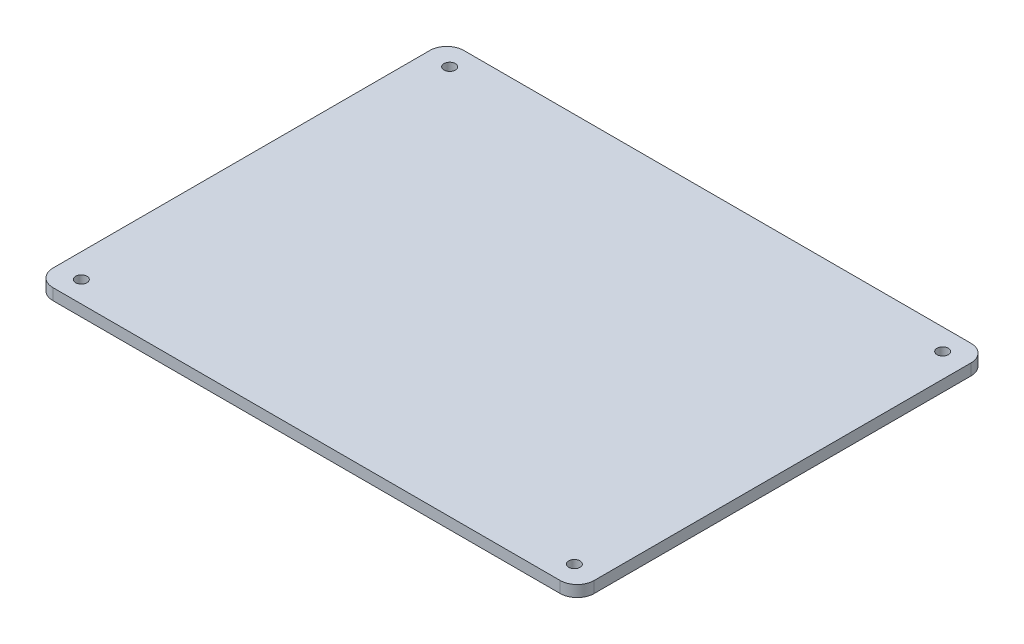
SolidWorks part; units mm, degrees
ref_plane "Спереди" through (0, 0, 0) normal (0, 0, 1) x (1, 0, 0)
ref_plane "Сверху" through (0, 0, 0) normal (0, 1, 0) x (1, 0, 0)
ref_plane "Справа" through (0, 0, 0) normal (1, 0, 0) x (0, 0, -1)
sketch "Эскиз1" plane through (0, 0, 0) normal (0, 1, 0) x (1, 0, 0)
  line L0 (-1000, 0) -> (49000, 0) construction
  line L1 (0, -1000) -> (0, 49000) construction
  line L2 (-1000, -35) -> (49000, -35) construction
  line L3 (-1000, 35) -> (49000, 35) construction
  line L4 (46.5, -1000) -> (46.5, 49000) construction
  line L5 (-46.5, -1000) -> (-46.5, 49000) construction
  line L10 (-47.75, -33.25) -> (-47.75, 33.25)
  line L11 (-44.75, -36.25) -> (44.75, -36.25)
  line L12 (47.75, -33.25) -> (47.75, 33.25)
  line L13 (-44.75, 36.25) -> (44.75, 36.25)
  line L15 (-47.75, -1000) -> (-47.75, 49000) construction
  line L16 (-1000, -36.25) -> (49000, -36.25) construction
  line L17 (-1000, 36.25) -> (49000, 36.25) construction
  line L18 (47.75, -1000) -> (47.75, 49000) construction
  arc A0 (-44.75, 36.25) -> (-47.75, 33.25) centre (-44.75, 33.25) ccw
  arc A1 (47.75, 33.25) -> (44.75, 36.25) centre (44.75, 33.25) ccw
  arc A2 (44.75, -36.25) -> (47.75, -33.25) centre (44.75, -33.25) ccw
  arc A3 (-44.75, -36.25) -> (-47.75, -33.25) centre (-44.75, -33.25) cw
  dimension "D5" = 3
  dimension "D1" = 1.25
  dimension "D2" = 1.25
  dimension "D3" = 1.25
  dimension "D4" = 1.25
extrude "Бобышка-Вытянуть1" add sketch "Эскиз1" along normal blind 2
sketch "Эскиз2" plane through (0, 2, 0) normal (0, 1, 0) x (1, 0, 0)
  line L0 (0, -1000) -> (0, 49000) construction
  line L1 (-1000, 0) -> (49000, 0) construction
  line L2 (43.5, -1000) -> (43.5, 49000) construction
  line L3 (-43.5, -1000) -> (-43.5, 49000) construction
  line L4 (-1000, -32.5) -> (49000, -32.5) construction
  line L5 (-1000, 32.5) -> (49000, 32.5) construction
  circle A0 centre (-43.5, 32.5) radius 2.5
  circle A1 centre (43.5, 32.5) radius 2.5
  circle A2 centre (43.5, -32.5) radius 2.5
  circle A3 centre (-43.5, -32.5) radius 2.5
sketch "Эскиз3" plane through (0, 5, 0) normal (0, 1, 0) x (1, 0, 0)
  circle A0 centre (-43.5, 32.5) radius 1
  circle A1 centre (-43.5, -32.5) radius 1
  circle A2 centre (43.5, -32.5) radius 1
  circle A3 centre (43.5, 32.5) radius 1
extrude "Вырез-Вытянуть1" cut sketch "Эскиз3" against normal blind 13 and the other way blind 3
sketch "Эскиз4" plane through (0, 0, 0) normal (0, -1, 0) x (1, 0, 0)
  line L0 (-1000, 0) -> (49000, 0) construction
  line L1 (0, -1000) -> (0, 49000) construction
  line L2 (19, -1000) -> (19, 49000) construction
  line L3 (-19, -1000) -> (-19, 49000) construction
  line L4 (-1000, -7) -> (49000, -7) construction
  line L5 (-1000, 7) -> (49000, 7) construction
  line L6 (-19, 7) -> (19, 7)
  line L7 (19, 7) -> (19, -7)
  line L8 (19, -7) -> (-19, -7)
  line L9 (-19, -7) -> (-19, 7)
extrude "Бобышка-Вытянуть3" add sketch "Эскиз4" along normal blind 3
sketch "Эскиз5" plane through (0, 0, 0) normal (0, -1, 0) x (1, 0, 0)
  line L0 (-17, -1004.1786) -> (-17, 48995.8214) construction
  line L2 (17, -1005.5591) -> (17, 48994.4409) construction
  line L4 (-1012.8566, 7) -> (48987.1434, 7) construction
  line L6 (-1011.4761, -7) -> (48988.5239, -7) construction
  line L8 (-17, -1004.1786) -> (-17, 48995.8214) construction
  line L9 (17, -1005.5591) -> (17, 48994.4409) construction
  line L11 (17, 7) -> (17, -7)
  line L13 (-17, -7) -> (-17, 7)
  line L14 (-19, 7) -> (-19, -7)
  line L15 (-19, -7) -> (-17, -7)
  line L16 (-19, 7) -> (-17, 7)
  line L17 (17, 7) -> (19, 7)
  line L18 (19, 7) -> (19, -7)
  line L19 (19, -7) -> (17, -7)
extrude "Вырез-Вытянуть3" cut sketch "Эскиз5" along normal blind 1.5
